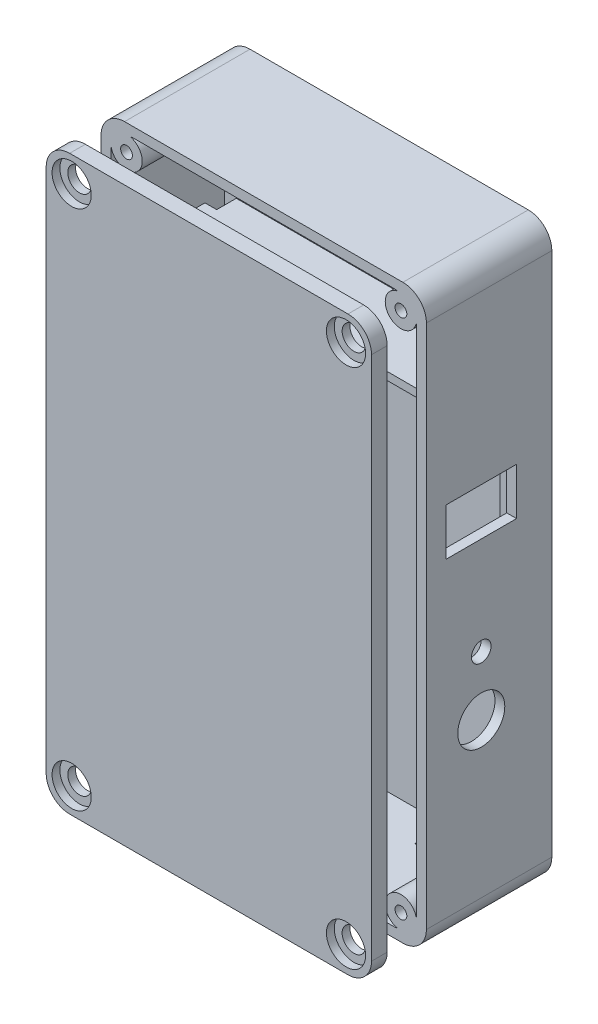
SolidWorks part; units mm, degrees
note: The reader was unsure of these and kept them because the rebuilt part matched: shared geometry of "Sketch2<3>", "Sketch2<4>", "Sketch6<3>", "Sketch11<4>", "Sketch6<4>".
other "Main box "
other "Main bolx cover"
ref_plane "Front Plane" through (0, 0, 0) normal (1, 0, 0) x (0, 1, 0)
ref_plane "Top Plane" through (0, 0, 0) normal (0, 0, 1) x (0, 1, 0)
ref_plane "Right Plane" through (0, 0, 0) normal (0, 1, 0) x (-1, 0, 0)
sketch "Sketch2" plane through (0, 0, 0) normal (0, 0, 1) x (0, 1, 0)
  line L0 (2.5, 24.5) -> (2.5, 90.5)
  line L1 (6, 16) -> (140, 16)
  line L2 (0, 22) -> (0, 93)
  line L3 (6, 99) -> (140, 99)
  line L4 (146, 22) -> (146, 93)
  line L5 (8.5, 96.5) -> (137.5, 96.5)
  line L6 (143.5, 24.5) -> (143.5, 90.5)
  line L7 (8.5, 18.5) -> (137.5, 18.5)
  line L8 (143.5, 18.5) -> (143.5, 96.5) construction
  line L9 (2.5, 96.5) -> (143.5, 96.5) construction
  line L10 (0, 99) -> (146, 99) construction
  line L11 (146, 16) -> (146, 99) construction
  line L12 (2.5, 18.5) -> (143.5, 18.5) construction
  line L13 (0, 16) -> (146, 16) construction
  line L14 (0, 16) -> (0, 99) construction
  line L15 (2.5, 18.5) -> (2.5, 96.5) construction
  arc A0 (2.5, 92.5) -> (6.5, 96.5) centre (6.5, 92.5) ccw
  arc A1 (139.5, 96.5) -> (143.5, 92.5) centre (139.5, 92.5) ccw
  arc A2 (143.5, 22.5) -> (139.5, 18.5) centre (139.5, 22.5) ccw
  arc A3 (6.5, 18.5) -> (2.5, 22.5) centre (6.5, 22.5) ccw
  arc A4 (143.5, 90.5) -> (137.5, 96.5) centre (137.5, 90.5) ccw
  arc A5 (140, 99) -> (146, 93) centre (140, 93) cw
  arc A6 (137.5, 18.5) -> (143.5, 24.5) centre (137.5, 24.5) ccw
  arc A7 (146, 22) -> (140, 16) centre (140, 22) cw
  arc A8 (0, 22) -> (6, 16) centre (6, 22) ccw
  arc A9 (2.5, 24.5) -> (8.5, 18.5) centre (8.5, 24.5) ccw
  arc A10 (2.5, 90.5) -> (8.5, 96.5) centre (8.5, 90.5) cw
  arc A11 (6, 99) -> (0, 93) centre (6, 93) ccw
  dimension "D6" = 8
  dimension "D7" = 6
  dimension "D4" = 78
  dimension "D5" = 146
  dimension "D1" = 2.5
  dimension "D2" = 2
  dimension "D3" = 2
extrude "box base" add sketch "Sketch2" along normal blind 3 contours A3 L7 A2 L6 A1 L5 A0 L0 | L7 A3 L0 | L6 A2 L7 | L5 A1 L6 | L0 A0 L5
extrude "box walls" add sketch "Sketch2<3>" along normal blind 32
sketch "Sketch2<3>" plane through (0, 0, 0) normal (0, 0, 1) x (0, 1, 0) same geometry as "Sketch2"
extrude "screw platforms" add sketch "Sketch2<4>" along normal blind 32 contours A10 A0 | A3 A9 | A1 A4 | A2 A6
sketch "Sketch2<4>" plane through (0, 0, 0) normal (0, 0, 1) x (0, 1, 0) same geometry as "Sketch2"
sketch "Sketch3" plane through (-67, 0, 32) normal (0, 0, -1) x (0, -1, 0)
  line L5 (-8.5, 29.5) -> (-137.5, 29.5) construction
  line L10 (-114.3, -48.5) -> (-135.5, -48.5)
  line L12 (-143.5, -42.5) -> (-143.5, 23.5) construction
  line L14 (-8.5, -48.5) -> (-137.5, -48.5) construction
  line L15 (-114.3, -48.5) -> (-112.3, -48.5)
  line L16 (-114.3, 29.5) -> (-112.3, 29.5)
  line L17 (-114.3, -45.2386) -> (-114.3, -48.5)
  line L23 (-114.3, 29.5) -> (-135.5, 29.5)
  line L24 (-135.5, -47.5996) -> (-135.5, -48.5)
  line L34 (-112.3, -48.5) -> (-112.3, 29.5)
  line L35 (-114.3, -45.2386) -> (-114.3, 29.5)
  line L37 (-135.5, -47.5996) -> (-135.5, 29.5)
  arc A1 (-143.3979, 24.6021) -> (-138.6021, 29.3979) centre (-139.5, 25.5) ccw construction
  point P0 (-140.5084, 30.4381)
  point P2 (-143.5, -9.5)
  point P5 (-140.5084, -49.4381)
  point P35 (-95.5634, -39.8777)
  dimension "D5" = 40.05
  dimension "D6" = 40.05
  dimension "D4" = 2
  dimension "D1" = 21.2
extrude "battery compartment" add sketch "Sketch3" against normal blind 19 from surface
sketch "Sketch5" plane through (0, 112.3, 0) normal (0, -1, 0) x (1, 0, 0)
  line L1 (-96.5, 3) -> (31.2509, 3)
  line L4 (-96.5, 3) -> (-18.5, 3)
  line L5 (-96.5, 3) -> (-18.5, 3)
  line L6 (-18.5, 3) -> (-18.5, 22)
  line L13 (-23.4229, 3) -> (-18.5, 3)
  line L20 (-96.5, 3) -> (-93.5, 3)
  line L21 (-96.5, 3) -> (-93.5, 3)
  line L22 (-96.5, 3) -> (-96.5, 8)
  line L23 (-96.5, 8) -> (-93.5, 8)
  line L32 (-93.5, 3) -> (-93.5, 8)
  line L33 (-18.5, 3) -> (-21.5, 3)
  line L34 (-18.5, 3) -> (-18.5, 8)
  line L35 (-18.5, 8) -> (-21.5, 8)
  line L36 (-21.5, 3) -> (-21.5, 8)
  line L37 (-21.5, 3) -> (105.3509, 3)
  line L42 (-18.5, 3) -> (-18.5, 22)
  line L46 (-18.5, 22) -> (-96.5, 22)
  line L47 (-18.5, 22) -> (-96.5, 22)
  line L48 (-96.5, 22) -> (-96.5, 3)
  line L49 (-96.5, 22) -> (-96.5, 3)
  point P22 (-96.5, 3)
  point P23 (-18.5, 3)
  line M9 (-96.5, 3) -> (-18.5, 3)
  dimension "D2" = 5
  dimension "D3" = 3
  dimension "D4" = 5
  dimension "D5" = 3
  dimension "D1" = 0
extrude "Cut-Extrude1" cut sketch "Sketch5" against normal blind 6 and the other way blind 3 contours L32 L23 L22 L5 M9 | L36 L5 L34 L35 M9
sketch "Sketch6" plane through (0, 0, 32) normal (0, 0, 1) x (1, 0, 0)
  line L1 (-24.5, 143.5) -> (-90.5, 143.5) construction
  line L4 (-16, 6) -> (-16, 140)
  line L5 (-22, 146) -> (-93, 146)
  line L6 (-99, 140) -> (-99, 6)
  line L7 (-93, 0) -> (-22, 0)
  line L8 (-16, 6) -> (-16, 140)
  line L9 (-22, 146) -> (-93, 146)
  line L10 (-99, 140) -> (-99, 6)
  line L11 (-93, 0) -> (-22, 0)
  line L12 (-24.5, 2.5) -> (-90.5, 2.5) construction
  line L17 (-18.5, 8.5) -> (-18.5, 137.5) construction
  line L18 (-96.5, 8.5) -> (-96.5, 137.5) construction
  line L19 (-96.5, 8.5) -> (-96.5, 137.5) construction
  line L20 (-96.5, 8.5) -> (-96.5, 137.5) construction
  line L21 (-25.5, 143.5) -> (-89.5, 143.5)
  line L22 (-25.5, 2.5) -> (-89.5, 2.5)
  line L23 (-18.5, 9.5) -> (-18.5, 136.5)
  line L24 (-96.5, 9.5) -> (-96.5, 136.5)
  line L25 (-96.5, 9.5) -> (-96.5, 137.5)
  line L26 (-96.5, 8.5) -> (-96.5, 136.5)
  arc A0 (-96.3979, 138.6021) -> (-91.6021, 143.3979) centre (-92.5, 139.5) ccw construction
  arc A1 (-91.6021, 2.6021) -> (-96.3979, 7.3979) centre (-92.5, 6.5) ccw construction
  arc A2 (-18.6021, 7.3979) -> (-23.3979, 2.6021) centre (-22.5, 6.5) ccw construction
  arc A3 (-96.3979, 138.6021) -> (-91.6021, 143.3979) centre (-92.5, 139.5) ccw
  arc A16 (-91.6021, 2.6021) -> (-96.3979, 7.3979) centre (-92.5, 6.5) ccw
  arc A17 (-18.6021, 7.3979) -> (-23.3979, 2.6021) centre (-22.5, 6.5) ccw
  circle A18 centre (-22.5, 139.5) radius 2.9975
  circle A19 centre (-92.5, 139.5) radius 5
  arc A20 (-99, 6) -> (-93, 0) centre (-93, 6) ccw
  arc A21 (-99, 6) -> (-93, 0) centre (-93, 6) ccw
  arc A22 (-22, 0) -> (-16, 6) centre (-22, 6) ccw
  arc A23 (-22, 0) -> (-16, 6) centre (-22, 6) ccw
  arc A24 (-16, 140) -> (-22, 146) centre (-22, 140) ccw
  arc A25 (-16, 140) -> (-22, 146) centre (-22, 140) ccw
  arc A26 (-93, 146) -> (-99, 140) centre (-93, 140) ccw
  arc A27 (-93, 146) -> (-99, 140) centre (-93, 140) ccw
  circle A28 centre (-92.5, 139.5) radius 2.9975
  circle A29 centre (-22.5, 139.5) radius 5
  circle A30 centre (-22.5, 6.5) radius 2.9975
  circle A31 centre (-22.5, 6.5) radius 5
  circle A32 centre (-92.5, 6.5) radius 2.9975
  circle A33 centre (-92.5, 6.5) radius 5
  circle A34 centre (-92.5, 139.5) radius 1.5
  circle A35 centre (-22.5, 139.5) radius 1.5
  circle A36 centre (-22.5, 6.5) radius 1.5
  circle A37 centre (-92.5, 6.5) radius 1.5
  arc A38 (-23.3979, 143.3979) -> (-18.6021, 138.6021) centre (-22.5, 139.5) ccw construction
  arc A39 (-23.3979, 143.3979) -> (-18.6021, 138.6021) centre (-22.5, 139.5) ccw
  dimension "D2" = 10
  dimension "D3" = 5.9951
  dimension "D6" = 3
  dimension "D1" = 0
  dimension "D4" = 2
  dimension "D5" = 2
  dimension "D7" = 2
  dimension "D8" = 2
extrude "box cover" add sketch "Sketch6" along normal blind 4 from offset 10 separate body
extrude "Boss-Extrude11" add sketch "Sketch6<3>" along normal blind 2 from offset 10
sketch "Sketch6<3>" plane through (0, 0, 32) normal (0, 0, 1) x (1, 0, 0) same geometry as "Sketch6"
sketch "Sketch8" plane through (0, 0, 3) normal (0, 0, 1) x (1, 0, 0)
  line L0 (-18.5, 8.5) -> (-18.5, 137.5) construction
  line L5 (-18.5, 11.3) -> (-24.5, 11.3)
  line L6 (-18.5, 11.3) -> (-18.5, 103.3784)
  line L8 (-24.5, 11.3) -> (-24.5, 103.3784)
  line L10 (-57.5, 143.5) -> (-57.5, 2.5)
  line L21 (-18.5, 103.3784) -> (-18.5, 95.5)
  line L23 (-24.5, 103.3784) -> (-24.5, 96.3)
  line L24 (-24.5, 143.5) -> (-90.5, 143.5) construction
  line L25 (-24.5, 2.5) -> (-90.5, 2.5) construction
  line L26 (-90.5, 103.3784) -> (-90.5, 96.3)
  line L28 (-96.5, 103.3784) -> (-96.5, 95.5)
  line L30 (-24.5, 103.3784) -> (-18.5, 103.3784)
  line L33 (-90.5, 11.3) -> (-90.5, 103.3784)
  line L35 (-96.5, 11.3) -> (-96.5, 103.3784)
  line L36 (-96.5, 11.3) -> (-90.5, 11.3)
  line L38 (-90.5, 103.3784) -> (-96.5, 103.3784)
  line M13 (-21.5, 112.3) -> (-93.5, 112.3)
  line M50 (-18.5, 8.5) -> (-18.5, 137.5)
  line M51 (-96.5, 137.5) -> (-96.5, 8.5)
  dimension "D2" = 6
extrude "rest platform" add sketch "Sketch8" along normal blind 1.7 contours L8 L5 L6 M50 M13 | L36 L33 L26 M51 M13
sketch "Sketch9" plane through (-16, 0, 0) normal (1, 0, 0) x (0, 1, 0)
  line L0 (6, 32) -> (140, 32) construction
  line L1 (85.3, 27) -> (97.3, 27)
  line L2 (85.3, 27) -> (85.3, 9)
  line L3 (85.3, 9) -> (97.3, 9)
  line L4 (97.3, 27) -> (97.3, 9)
  line L5 (112.3, 22) -> (112.3, 8) construction
  circle A0 centre (45.3, 18) radius 6
  circle A1 centre (60.3945, 18) radius 2.5
  point P10 (85.3, 18)
  dimension "D5" = 12
  dimension "D7" = 5
  dimension "D1" = 18
  dimension "D2" = 12
  dimension "D3" = 5
  dimension "D4" = 15
  dimension "D6" = 40
extrude "buttton holes" cut sketch "Sketch9" against normal blind 4
sketch "Sketch10" plane through (0, 0, 0) normal (0, -1, 0) x (1, 0, 0)
  line L0 (-22, 0) -> (-93, 0) construction
  line L1 (-39.943, 5) -> (-26.943, 5)
  line L2 (-39.943, 5) -> (-39.943, 11)
  line L3 (-39.943, 11) -> (-26.943, 11)
  line L4 (-26.943, 5) -> (-26.943, 11)
  dimension "D1" = 13
  dimension "D2" = 6
  dimension "D3" = 5
extrude "fake usb" cut sketch "Sketch10" against normal blind 4
sketch "Sketch11" plane through (0, 0, 32) normal (0, 0, 1) x (1, 0, 0)
  line L0 (-96.5, 103.3784) -> (-96.5, 137.5) construction
  line L1 (-96.5, 112.3) -> (-67.5, 112.3)
  line L2 (-96.5, 112.3) -> (-96.5, 83.3)
  line L3 (-96.5, 83.3) -> (-67.5, 83.3)
  line L4 (-67.5, 112.3) -> (-67.5, 83.3)
  line L5 (-65.5, 112.3) -> (-65.5, 81.3)
  line L6 (-96.5, 81.3) -> (-65.5, 81.3)
  line L9 (-98.5, 114.3) -> (-98.5, 81.3) construction
  line L10 (-98.5, 114.3) -> (-65.5, 114.3) construction
  line L12 (-18.5, 112.3) -> (-96.5, 112.3) construction
  line L13 (-96.5, 83.3) -> (-96.5, 81.3)
  line L14 (-98.5, 81.3) -> (-65.5, 81.3) construction
  line L15 (-65.5, 114.3) -> (-65.5, 81.3) construction
  line L16 (-96.5, 81.3) -> (-96.5, 83.3)
  line L18 (-96.5, 112.3) -> (-96.5, 114.3)
  line L19 (-96.5, 114.3) -> (-67.5, 114.3)
  line L20 (-96.5, 114.3) -> (-18.5, 114.3) construction
  line L22 (-65.5, 112.3) -> (-65.5, 114.3)
  line L23 (-93.5, 114.3) -> (-21.5, 114.3) construction
  line L24 (-65.5, 114.3) -> (-67.5, 114.3)
  dimension "D1" = 29
  dimension "D2" = 29
  dimension "D3" = 2
extrude "gps antenna box" add sketch "Sketch11" against normal blind 2 from offset 10 contours L2 L1 L4 L3 offset against normal yes
extrude "gps antenna box walls" add sketch "Sketch11<4>" along normal blind 5 from offset 12 offset against normal yes
sketch "Sketch11<4>" plane through (0, 0, 32) normal (0, 0, 1) x (1, 0, 0) same geometry as "Sketch11"
sketch "Sketch12" plane through (0, 81.3, 0) normal (0, -1, 0) x (1, 0, 0)
  line L0 (-96.5, 25) -> (-65.5, 25) construction
  line L1 (-82, 25) -> (-80, 25)
  line L2 (-82, 25) -> (-82, 22)
  line L3 (-82, 22) -> (-80, 22)
  line L4 (-80, 25) -> (-80, 22)
  point P6 (-81, 25)
  dimension "D1" = 2
  dimension "D2" = 3
extrude "Cut-Extrude4" cut sketch "Sketch12" against normal blind 4
extrude "Cut-Extrude5" cut sketch "Sketch6<4>" against normal blind 10 contours A34 | A35 | A36 | A37 | A18 | A32
sketch "Sketch6<4>" plane through (0, 0, 32) normal (0, 0, 1) x (1, 0, 0) same geometry as "Sketch6"
